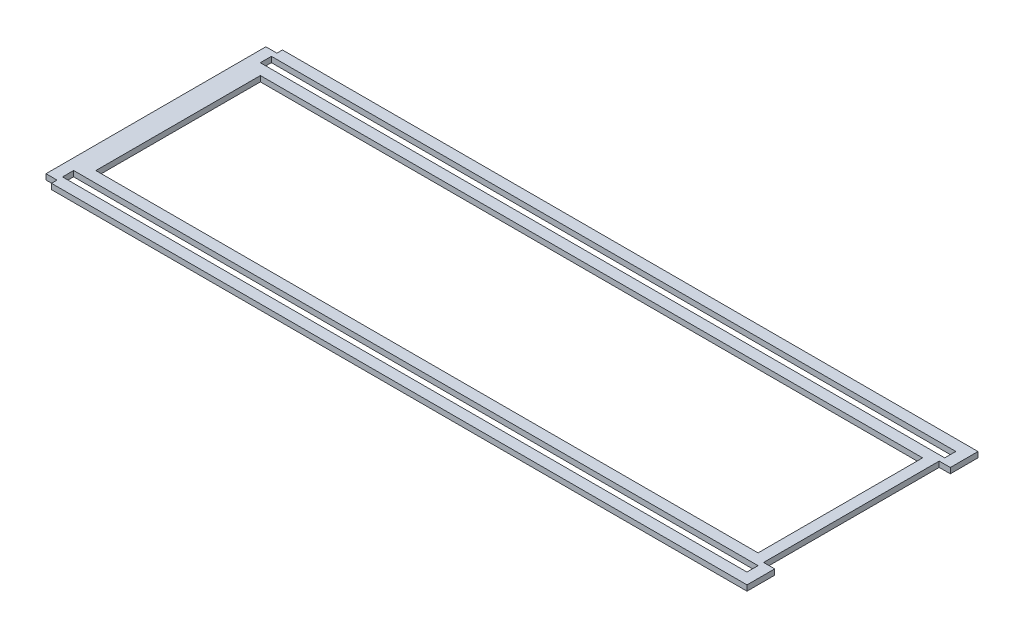
SolidWorks part; units mm, degrees
ref_plane "Front" through (0, 0, 0) normal (0, 0, 1) x (1, 0, 0)
ref_plane "Top" through (0, 0, 0) normal (0, 1, 0) x (1, 0, 0)
ref_plane "Right" through (0, 0, 0) normal (1, 0, 0) x (0, 0, -1)
sketch "Sketch1" plane through (0, 0, 0) normal (0, 1, 0) x (1, 0, 0)
  line L0 (-203.2, 63.2269) -> (-203.2, -58.2454)
  line L1 (-196.85, 66.4273) -> (203.2, 66.4273)
  line L3 (-196.85, -66.4273) -> (203.2, -66.4273)
  line L4 (203.2, 66.4273) -> (203.2, 50.5016)
  line L5 (0, 0) -> (-84.4016, 0) construction
  line L6 (-183.7755, -60.0774) -> (-164.1955, -53.6766) construction
  line L7 (-196.85, 60.0773) -> (196.7992, 60.0773)
  line L9 (-196.85, 53.6766) -> (196.7992, 53.6766)
  line L10 (196.7992, 60.0773) -> (196.7992, 53.6766)
  line L11 (-196.85, -53.6766) -> (196.7992, -53.6765)
  line L13 (-196.85, -60.0774) -> (196.7992, -60.0774)
  line L14 (196.7992, -53.6765) -> (196.7992, -60.0774)
  line L16 (203.2, -50.5016) -> (203.2, -66.4273)
  line L17 (203.2, 50.5016) -> (196.7992, 50.5016)
  line L19 (203.2, -50.5016) -> (196.7992, -50.5016)
  line L20 (196.7992, 50.5016) -> (196.7992, -50.5016)
  line L21 (142.9078, -53.6766) -> (203.2, -66.4273) construction
  line L30 (164.1955, 53.6766) -> (203.2, 66.4273) construction
  line L32 (0, -24.3249) -> (0, 0) construction
  line L35 (-203.2, -58.2454) -> (-203.2, -63.2269)
  line L37 (-196.85, -53.6766) -> (-196.85, -60.0774)
  line L41 (-196.85, 53.6766) -> (-196.85, 60.0773)
  line L48 (-203.2, -63.2269) -> (-196.85, -63.2269)
  line L49 (-196.85, -66.4273) -> (-196.85, -63.2269)
  line L50 (-203.2, 63.2269) -> (-196.85, 63.2269)
  line L53 (-196.85, 63.2269) -> (-196.85, 66.4273)
  line L54 (-190.4492, 47.3265) -> (190.4492, 47.3265)
  line L55 (-190.4492, 47.3265) -> (-190.4492, -47.3266)
  line L56 (-190.4492, -47.3266) -> (190.4492, -47.3265)
  line L57 (190.4492, 47.3265) -> (190.4492, -47.3265)
  line L58 (-190.4492, 47.3265) -> (190.4492, -47.3265) construction
  line L59 (-190.4492, -47.3266) -> (190.4492, 47.3265) construction
  point P0 (0, 0)
  point P12 (0, 0)
  dimension "D3" = 6.4008
  dimension "D4" = 6.35
  dimension "D5" = 6.35
  dimension "D6" = 6.4008
  dimension "D7" = 3.175
  dimension "D8" = 3.175
  dimension "D2" = 406.4
  dimension "D11" = 203.2
  dimension "D9" = 393.6492
  dimension "D12" = 3.2004
  dimension "D13" = 3.2004
  dimension "D14" = 6.35
  dimension "D15" = 6.35
extrude "Boss-Extrude1" add sketch "Sketch1" along normal blind 3.175
equation "\"D1@Sketch1\"      = 5.59025 - 0.25 - 0.016 - ( 6 / 64 )"
equation "\"D10@Sketch1\"=\"D1@Sketch1\"/2"
